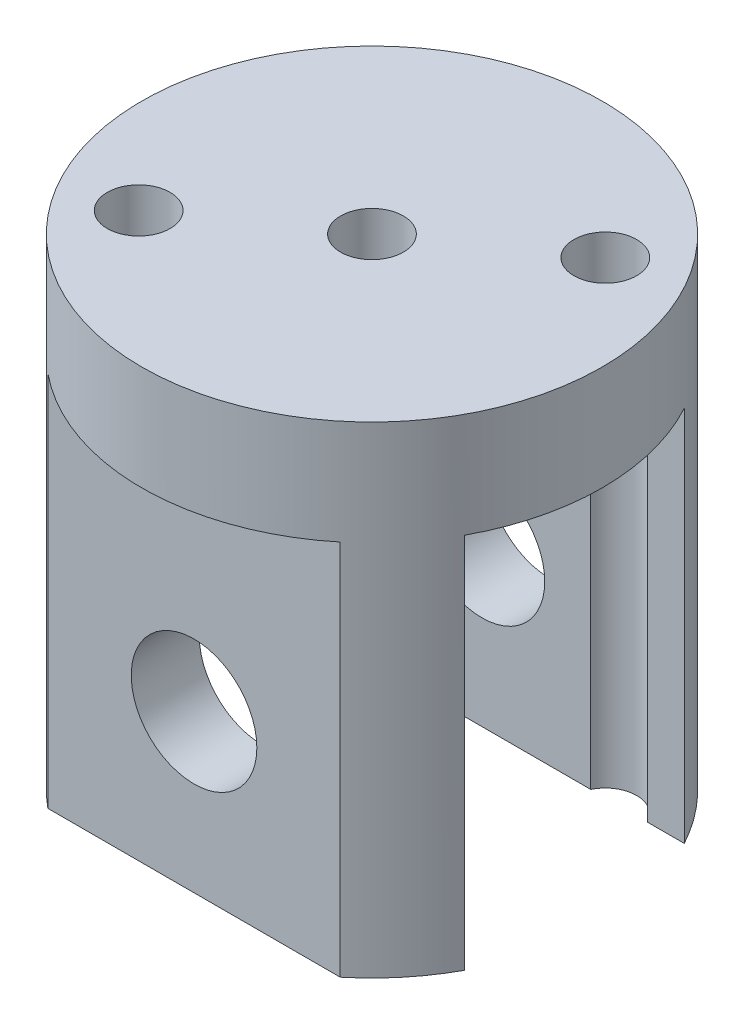
SolidWorks part; units mm, degrees
ref_plane "前视基准面" through (0, 0, 0) normal (0, 0, 1) x (1, 0, 0)
ref_plane "上视基准面" through (0, 0, 0) normal (0, 1, 0) x (1, 0, 0)
ref_plane "右视基准面" through (0, 0, 0) normal (1, 0, 0) x (0, 0, -1)
other "Configuration Table"
sketch "草图2" plane through (0, 0, 0) normal (0, 1, 0) x (1, 0, 0)
  circle A0 centre (0, 0) radius 11
  dimension "D1" = 22
extrude "凸台-拉伸1" add sketch "草图2" along normal blind 23
sketch "草图3" plane through (0, 0, 0) normal (0, 0, 1) x (1, 0, 0)
  line L1 (-11, 0) -> (19, 0)
  line L2 (-11, 0) -> (-11, 18)
  line L3 (-11, 18) -> (19, 18)
  line L4 (19, 0) -> (19, 18)
  dimension "D1" = 18
  dimension "D2" = 30
extrude "切除-拉伸1" cut sketch "草图3" against normal through all from offset 8.5 contours L2 L3 L4 L1 offset against normal yes
extrude "切除-拉伸2" cut sketch "草图3<5>" along normal through all from offset 8.5
sketch "草图3<5>" plane through (0, 0, 0) normal (0, 0, 1) x (1, 0, 0) same geometry as "草图3"
extrude "切除-拉伸3" cut sketch "草图3<6>" against normal mid plane 10.5
sketch "草图3<6>" plane through (0, 0, 0) normal (0, 0, 1) x (1, 0, 0) same geometry as "草图3"
sketch "草图4" plane through (0, 0, 8.5) normal (0, 0, 1) x (1, 0, 0)
  line L0 (0, 0) -> (0, 14.5796) construction
  circle A0 centre (0, 7.5) radius 3
  dimension "D1" = 6
  dimension "D2" = 7.5
extrude "切除-拉伸4" cut sketch "草图4" against normal through all
sketch "草图6" plane through (0, 23, 0) normal (0, 1, 0) x (1, 0, 0)
  circle A0 centre (0, 0) radius 1.5
  dimension "D1" = 3
extrude "切除-拉伸5" cut sketch "草图6" against normal through all contours A0
sketch "草图7" plane through (0, 0, -8.5) normal (0, 0, -1) x (-1, 0, 0)
  line L0 (0, 7.5) -> (16.276, 7.5) construction
sketch "草图8" plane through (0, 23, 0) normal (0, 1, 0) x (1, 0, 0)
  circle A0 centre (-6.548, -4.5961) radius 1.5
  circle A3 centre (6.548, 4.5961) radius 1.5
extrude "切除-拉伸6" cut sketch "草图8" against normal through all
